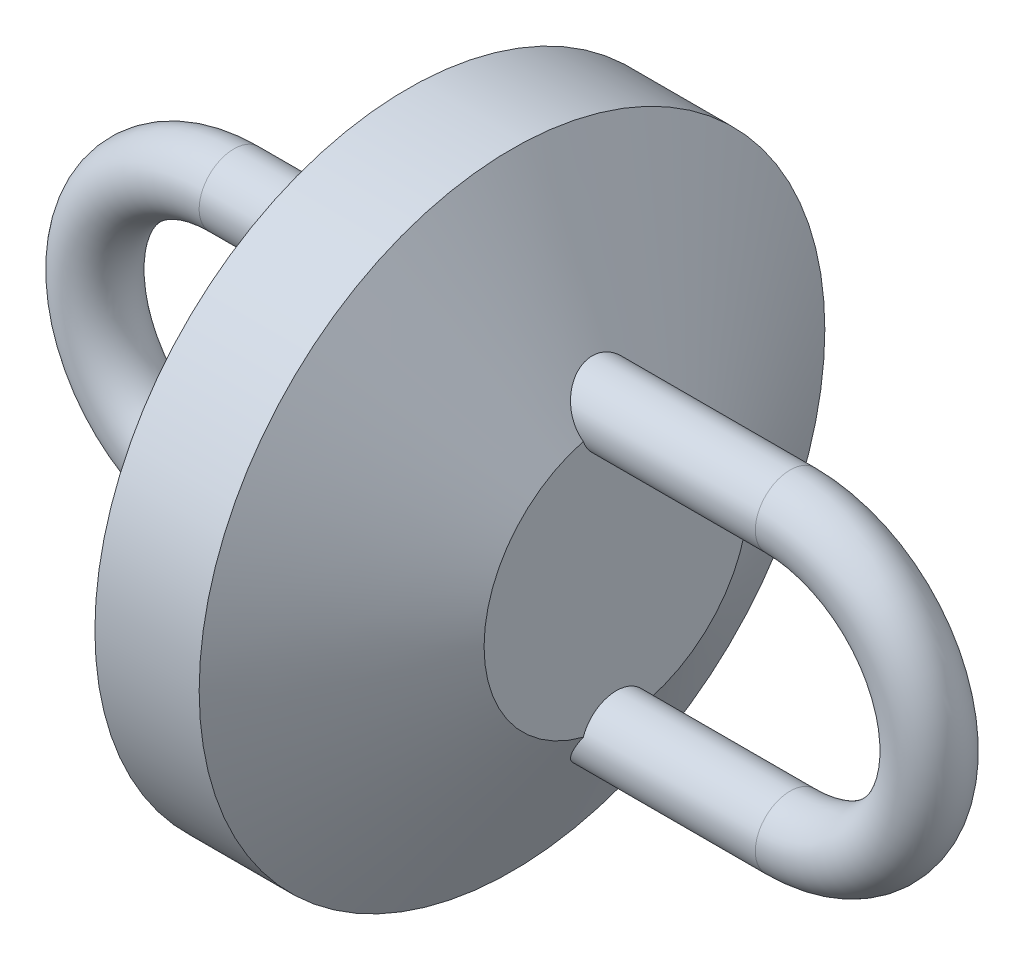
SolidWorks part; units mm, degrees
ref_plane "前视基准面" through (0, 0, 0) normal (0, 0, 1) x (1, 0, 0)
ref_plane "上视基准面" through (0, 0, 0) normal (0, 1, 0) x (1, 0, 0)
ref_plane "右视基准面" through (0, 0, 0) normal (1, 0, 0) x (0, 0, -1)
other "Configuration Table"
sketch "草图1" plane through (0, 0, 0) normal (0, 0, 1) x (1, 0, 0)
  line L1 (8, 4) -> (-8, 4)
  line L2 (8, 4) -> (8, -4) construction
  line L3 (8, -4) -> (-8, -4)
  line L4 (-8, 4) -> (-8, -4) construction
  line L5 (8, 4) -> (-8, -4) construction
  line L6 (8, -4) -> (-8, 4) construction
  arc A0 (-8, -4) -> (-8, 4) centre (-8, 0) cw
  arc A1 (8, 4) -> (8, -4) centre (8, 0) cw
  point P0 (0, 0)
  point P6 (-12, 0)
  point P9 (12, 0)
  dimension "D1" = 8
  dimension "D2" = 24
sweep "扫描1" add path "草图1" circular profile diameter 2 parameters "D3"=2
sketch "草图9" plane through (0, 0, 0) normal (1, 0, 0) x (0, 0, -1)
  circle A0 centre (0, 0) radius 9
  dimension "D1" = 18
extrude "凸台-拉伸1" add sketch "草图9" along normal blind 3 draft 60 and the other way blind 3
sketch "草图10" plane through (0, 0, 0) normal (0, 0, 1) x (1, 0, 0)
  line L0 (-12.2984, 0) -> (15.1477, 0) construction
  line L1 (0, 9.2191) -> (0, -10.682) construction
  circle A0 centre (-10, 0) radius 1
  arc A1 (-8, 3) -> (-8, -3) centre (-8, 0) ccw construction
  circle A2 centre (10, 0) radius 1
  dimension "D1" = 2
